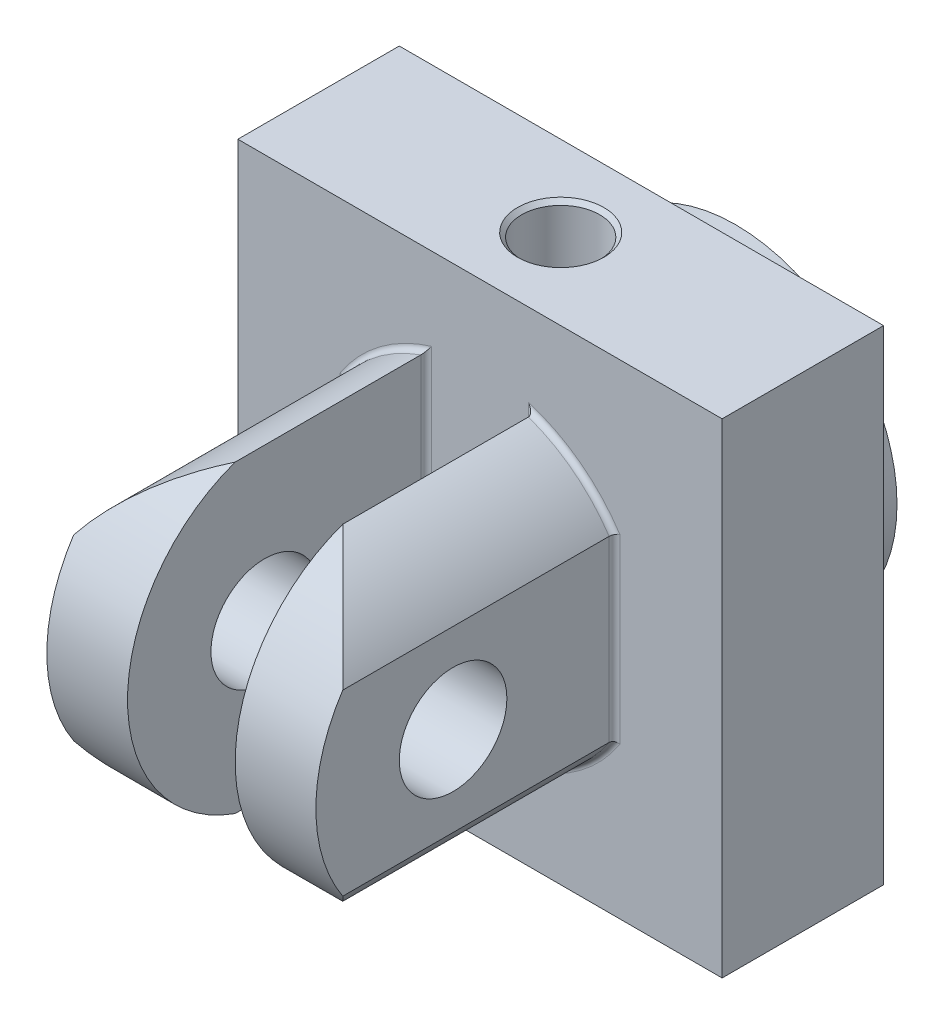
SolidWorks part; units mm, degrees
ref_plane "Front Plane" through (0, 0, 0) normal (0, 0, 1) x (1, 0, 0)
ref_plane "Top Plane" through (0, 0, 0) normal (0, 1, 0) x (1, 0, 0)
ref_plane "Right Plane" through (0, 0, 0) normal (1, 0, 0) x (0, 0, -1)
ref_plane "Otsapinta" through (0, 0, 17.5) normal (0, 0, 1) x (1, 0, 0)
ref_plane "77,5" through (0, 0, 77.5) normal (0, 0, 1) x (1, 0, 0)
ref_axis "Axis1" through (88.99, 0, 77.5) along (-1, 0, 0)
sketch "Sketch2" plane through (0, 0, 0) normal (0, 0, 1) x (1, 0, 0)
  line L1 (-45, 45) -> (45, 45)
  line L2 (-45, 45) -> (-45, -45)
  line L3 (-45, -45) -> (45, -45)
  line L4 (45, 45) -> (45, -45)
  point P4 (0, 45)
  point P7 (45, 0)
  dimension "D1" = 90
  dimension "D2" = 90
extrude "Boss-Extrude1" add sketch "Sketch2" along normal blind 103
sketch "Sketch3" plane through (0, 0, 0) normal (0, 1, 0) x (1, 0, 0)
  line L0 (0, 0) -> (0, -108.3396) construction
sketch "Sketch4" plane through (0, 0, 0) normal (0, 1, 0) x (1, 0, 0)
  line L0 (0, 0) -> (30, 0)
  line L1 (-49.5, 0) -> (49.5, 0) construction
  line L2 (30, 0) -> (30, -2.5)
  line L3 (30, 0) -> (70, 0)
  line L4 (30, 0) -> (30, -17.5)
  line L5 (30, -17.5) -> (70, -17.5)
  line L6 (70, 0) -> (70, -17.5)
  line L7 (0, -25) -> (0, -39.4207)
  line L8 (30, -2.5) -> (27, -2.5)
  line L9 (30, -2.5) -> (30, -6.5)
  line L10 (30, -6.5) -> (27, -6.5)
  line L11 (27, -2.5) -> (27, -6.5)
  line L12 (0, 0) -> (24, 0)
  line L13 (0, 0) -> (0, -25)
  line L14 (0, -25) -> (24, -25)
  line L15 (24, 0) -> (24, -25)
  line L16 (0, 0) -> (0, -108.3396) construction
  line L17 (0, -39.4207) -> (24, -25)
  dimension "D1" = 30
  dimension "D2" = 40
  dimension "D3" = 17.5
  dimension "D4" = 4
  dimension "D5" = 3
  dimension "D6" = 24
  dimension "D7" = 25
  dimension "D8" = 31
revolve "Cut-Revolve2" cut sketch "Sketch4" angle 360 about L0 region at (12, 0, 12.5) region at (8, 0, 29.8069)
sketch "Sketch5" plane through (0, 0, 0) normal (1, 0, 0) x (0, 0, -1)
  circle A0 centre (-77.5, 0) radius 10
extrude "Cut-Extrude1" cut sketch "Sketch5" against normal through all both and the other way through all
sketch "Sketch6" plane through (0, 0, 0) normal (1, 0, 0) x (0, 0, -1)
  line L0 (-77.5, 0) -> (-47.5, 0)
  line L3 (0, 0) -> (-108.3396, 0) construction
  line L4 (-47.5, 0) -> (-47.5, 30)
  line L7 (-47.5, 30) -> (-134.6694, 30)
  line L8 (-47.5, 30) -> (-47.5, 73.1012)
  line L9 (-47.5, 73.1012) -> (-134.6694, 73.1012)
  line L10 (-134.6694, 30) -> (-134.6694, 73.1012)
revolve "Cut-Revolve3" cut sketch "Sketch6" angle 360 about L0 region at (0, 51.5506, 91.0847)
sketch "Sketch7" plane through (0, 0, 0) normal (1, 0, 0) x (0, 0, -1)
  line L0 (-103, 0) -> (-73, 0)
  line L1 (-103, 30) -> (-103, -30) construction
  line L2 (0, 0) -> (-108.3396, 0) construction
  line L3 (-77.5, 49.5) -> (-77.5, -49.5) construction
  line L4 (-103, 30) -> (-77.5, 30)
  line L5 (-103, 30) -> (-103, -30)
  line L6 (-103, -30) -> (-77.5, -30)
  line L7 (-77.5, 30) -> (-77.5, -30)
  line L8 (-103, -30) -> (-47.5, -30) construction
  circle A0 centre (-73, 0) radius 30
extrude "Cut-Extrude2" cut sketch "Sketch7" against normal through all both and the other way through all contours A0 L7 L4 L5 | A0 L5 L6 L7 region at (0, -23.2816, 96.3515) region at (0, 23.2816, 96.3515)
sketch "Sketch8" plane through (0, 0, 47.5) normal (0, 0, 1) x (1, 0, 0)
  line L1 (-10, 35) -> (10, 35)
  line L2 (-10, 35) -> (-10, -35)
  line L3 (-10, -35) -> (10, -35)
  line L4 (10, 35) -> (10, -35)
  line L5 (-25, 35) -> (25, 35)
  line L6 (-25, 35) -> (-25, -35)
  line L7 (-25, -35) -> (25, -35)
  line L8 (25, 35) -> (25, -35)
  circle A0 centre (0, 0) radius 30
  point P7 (10, 0)
  point P8 (0, -35)
  point P13 (25, 0)
  point P14 (0, 35)
  circle M9 centre (0, 0) radius 30
  dimension "D1" = 20
  dimension "D2" = 70
  dimension "D3" = 50
  dimension "D4" = 70
extrude "Cut-Extrude3" cut sketch "Sketch8" along normal blind 103 contours L8 M9 | L6 M9 | L4 L2 M9 region at (0, 0, 47.5) region at (-27.015, 0, 47.5) region at (27.015, 0, 47.5)
sketch "Sketch10" plane through (0, 45, 0) normal (0, 1, 0) x (1, 0, 0)
  line L0 (0, -17.5) -> (0, -32.5)
  line L2 (0, 0) -> (0, -108.3396) construction
  line L3 (-49.5, -17.5) -> (49.5, -17.5) construction
  circle A0 centre (0, -32.5) radius 1.7
  dimension "D1" = 3.4
extrude "Cut-Extrude4" cut sketch "Sketch10" against normal up to next contours A0
fillet "Fillet1" radius 1 9 edges at (-10, 0, 47.5) (-18.4521, 23.6542, 47.5) (-25, 0, 47.5) (-18.4521, -23.6542, 47.5) (10, 0, 47.5) (18.4521, -23.6542, 47.5) (25, 0, 47.5) (18.4521, 23.6542, 47.5) (-30, 0, 17.5)
sketch "Sketch14" plane through (0, 0, 17.5) normal (0, 0, -1) x (-1, 0, 0)
  line L0 (0, 0) -> (-45, 45)
  circle A0 centre (0, 0) radius 45
sketch "Sketch17" plane through (0, 45, 0) normal (0, 1, 0) x (1, 0, 0)
  line L0 (0, -17.5) -> (0, -32.5)
  line L1 (45, -17.5) -> (-45, -17.5) construction
  line L2 (0, 0) -> (0, -108.3396) construction
  dimension "D1" = 15
hole_wizard "M16x1.5 Tapped Hole2" positions "Sketch20" profile "Sketch21" tap size "M16x1.5" standard "ANSI Metric"
sketch "Sketch20" plane through (0, 45, 0) normal (0, 1, 0) x (1, 0, 0)
  point P0 (0, -32.5)
sketch "Sketch21" plane through (0, 45, 32.5) normal (1, 0, 0) x (0, 0, 1)
  line L0 (0, 0) -> (0, 24.3562)
  line L1 (0, 24.3562) -> (7.25, 20)
  line L2 (7.25, 20) -> (7.25, 0.775)
  line L3 (7.25, 0.775) -> (8.025, 0)
  line L5 (8.025, 0) -> (0, 0)
  line L6 (-7.25, 0.775) -> (-8.025, 0) construction
  line L10 (0, 24.3562) -> (-7.25, 20) construction
  line L11 (0, -6.35) -> (0, 107.95) construction
  dimension "Tap Drill Dia." = 14.5
  dimension "Tap Drill Depth" = 20
  dimension "Near C'Sink Dia." = 16.05
  dimension "Near C'Sink Angle" = 90
  dimension "Drill Angle" = 118
cosmetic thread "Hole Thread2" parameters "D1"=15, "D2"=16
hole_wizard "M12x1.5 Tapped Hole1" positions "Sketch24" profile "Sketch25" tap size "M12x1.5" standard "ANSI Metric"
sketch "Sketch24" plane through (0, 0, 17.5) normal (0, 0, -1) x (-1, 0, 0)
  line L0 (0, 0) -> (-45, 45) construction
  circle A0 centre (0, 0) radius 45 construction
  point P0 (-31.8198, 31.8198)
sketch "Sketch25" plane through (31.8198, 31.8198, 17.5) normal (1, 0, 0) x (0, 1, 0)
  line L0 (0, 0) -> (0, 23.1545)
  line L1 (0, 23.1545) -> (5.25, 20)
  line L2 (5.25, 20) -> (5.25, 0.775)
  line L3 (5.25, 0.775) -> (6.025, 0)
  line L5 (6.025, 0) -> (0, 0)
  line L6 (-5.25, 0.775) -> (-6.025, 0) construction
  line L10 (0, 23.1545) -> (-5.25, 20) construction
  line L11 (0, -6.35) -> (0, 107.95) construction
  dimension "Tap Drill Dia." = 10.5
  dimension "Tap Drill Depth" = 20
  dimension "Near C'Sink Dia." = 12.05
  dimension "Near C'Sink Angle" = 90
  dimension "Drill Angle" = 118
cosmetic thread "Hole Thread3" parameters "D1"=15, "D2"=12
pattern_circular "CirPattern2" count 4 every 90 about axis through (0, 0, 0) along (0, 0, 1) of "M12x1.5 Tapped Hole1"
cosmetic thread "Hole Thread4" parameters "D1"=15, "D2"=12
cosmetic thread "Hole Thread5" parameters "D1"=15, "D2"=12
cosmetic thread "Hole Thread6" parameters "D1"=15, "D2"=12
